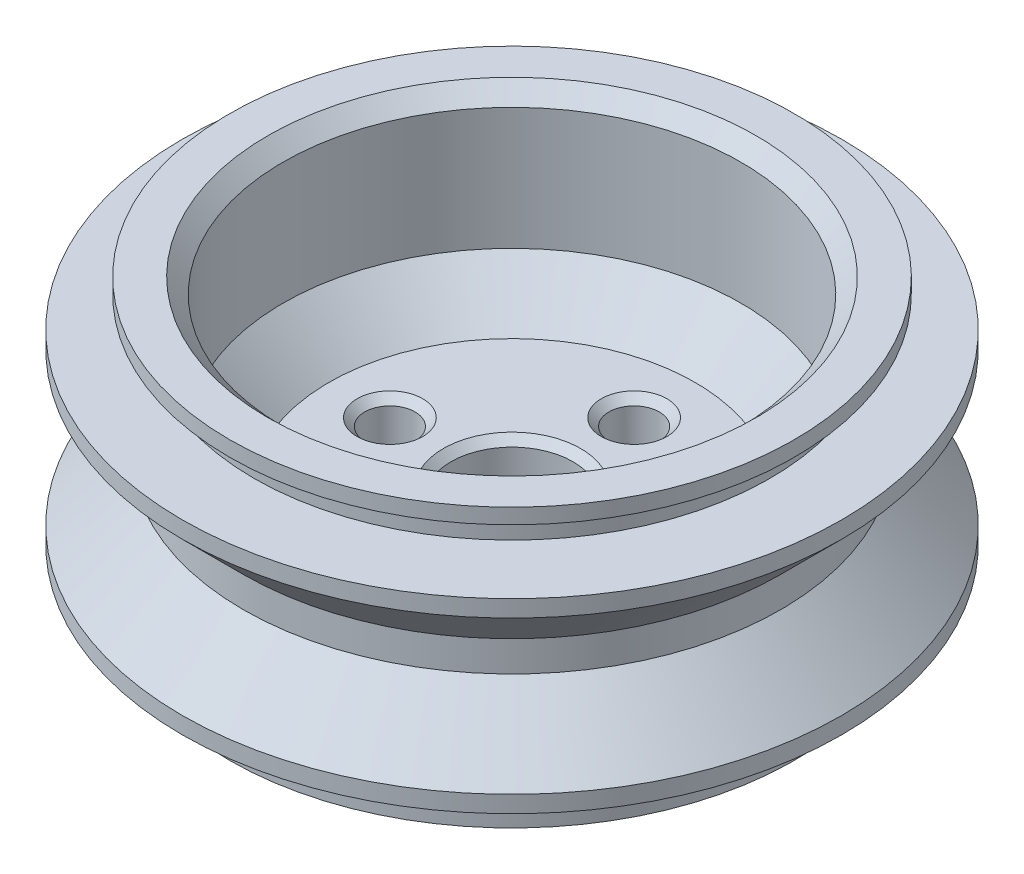
SolidWorks part; units mm, degrees
ref_plane "前视基准面" through (0, 0, 0) normal (0, 0, 1) x (1, 0, 0)
ref_plane "上视基准面" through (0, 0, 0) normal (0, 1, 0) x (1, 0, 0)
ref_plane "右视基准面" through (0, 0, 0) normal (1, 0, 0) x (0, 0, -1)
other "Configuration Table"
sketch "草图1" plane through (0, 0, 0) normal (0, 1, 0) x (1, 0, 0)
  circle A0 centre (0, 0) radius 21.6
  dimension "D1" = 43.2
extrude "凸台-拉伸1" add sketch "草图1" along normal mid plane 18.2
sketch "草图2" plane through (0, 0, 0) normal (0, 0, 1) x (1, 0, 0)
  line L0 (21.6, -9.1) -> (21.6, 9.1) construction
  line L1 (21.6, -8.1) -> (16.9, -8.1)
  line L2 (21.6, -8.1) -> (21.6, -6.1)
  line L3 (21.6, -6.1) -> (16.9, -6.1)
  line L4 (16.9, -8.1) -> (16.9, -6.1)
  line L5 (-21.6, -9.1) -> (21.6, -9.1) construction
  line L6 (18.5, -9.1) -> (21.6, -9.1)
  line L7 (18.5, -9.1) -> (18.5, -8.1)
  line L8 (18.5, -8.1) -> (21.6, -8.1)
  line L9 (21.6, -9.1) -> (21.6, -8.1)
  dimension "D1" = 4.7
  dimension "D2" = 18.5
  dimension "D3" = 3
  dimension "D4" = 1
ref_axis "基准轴1" through (0, 9.1, 0) along (0, -1, 0)
revolve "切除-旋转1" cut sketch "草图2" angle 360 about axis through (0, 9.1, 0) along (0, -1, 0) region at (20.05, -8.6, 0) region at (19.25, -7.1, 0)
mirror "镜向1" about plane through (0, 0, 0) normal (0, 1, 0) of "切除-旋转1"
sketch "草图3" plane through (0, -9.1, 0) normal (0, -1, 0) x (1, 0, 0)
  circle A0 centre (0, 0) radius 15
  dimension "D1" = 30
extrude "切除-拉伸1" cut sketch "草图3" against normal blind 3
sketch "草图4" plane through (0, -6.1, 0) normal (0, -1, 0) x (1, 0, 0)
  circle A0 centre (0, 0) radius 4
  dimension "D1" = 8
extrude "切除-拉伸2" cut sketch "草图4" against normal blind 20
sketch "草图5" plane through (0, -6.1, 0) normal (0, -1, 0) x (1, 0, 0)
  circle A0 centre (-8, 0) radius 1.65
  point P2 (0, 0)
  dimension "D2" = 3.3
  dimension "D1" = 8
extrude "切除-拉伸3" cut sketch "草图5" against normal blind 20
pattern_circular "阵列(圆周)1" count 4 over 360 about axis through (0, 9.1, 0) along (0, -1, 0) of "切除-拉伸3"
extrude "切除-拉伸4" cut sketch "草图3<2>" along normal blind 12 from surface starting at face at (0, 9.1, -6.35)
sketch "草图3<2>" plane through (0, -9.1, 0) normal (0, -1, 0) x (1, 0, 0) same geometry as "草图3"
sketch "草图6" plane through (0, 0, 0) normal (0, 0, 1) x (1, 0, 0)
  line L5 (21.6, -6.1) -> (21.6, 6.1) construction
  line L6 (17.6, -5) -> (21.6, -5)
  line L7 (17.6, -5) -> (17.6, 5)
  line L8 (17.6, 5) -> (21.6, 5)
  line L9 (21.6, -5) -> (21.6, 5)
  line L10 (17.6, -5) -> (21.6, 5) construction
  line L11 (17.6, 5) -> (21.6, -5) construction
  point P0 (19.6, 0)
  point P7 (0, 0)
  dimension "D1" = 4
  dimension "D2" = 10
revolve "切除-旋转2" cut sketch "草图6" angle 360 about axis through (0, 9.1, 0) along (0, -1, 0)
chamfer "倒角1" distance 4 angle 45 2 edges at (0, -5, 17.6) (0, 5, 17.6)
chamfer "倒角2" distance 3 angle 45 2 edges at (0, -6.1, -15) (0, -2.9, 15)
chamfer "倒角3" distance 1 angle 45 1 edges at (0, 9.1, 15)
chamfer "倒角4" distance 0.5 angle 45 10 edges at (0, -2.9, -6.35) (1.65, -6.1, -8) (-8, -2.9, 1.65) (-8, -6.1, -1.65) (8, -2.9, 1.65) (8, -6.1, 1.65) (0, -2.9, 4) (0, -6.1, -4) (0, -2.9, 9.65) (-1.65, -6.1, 8)
